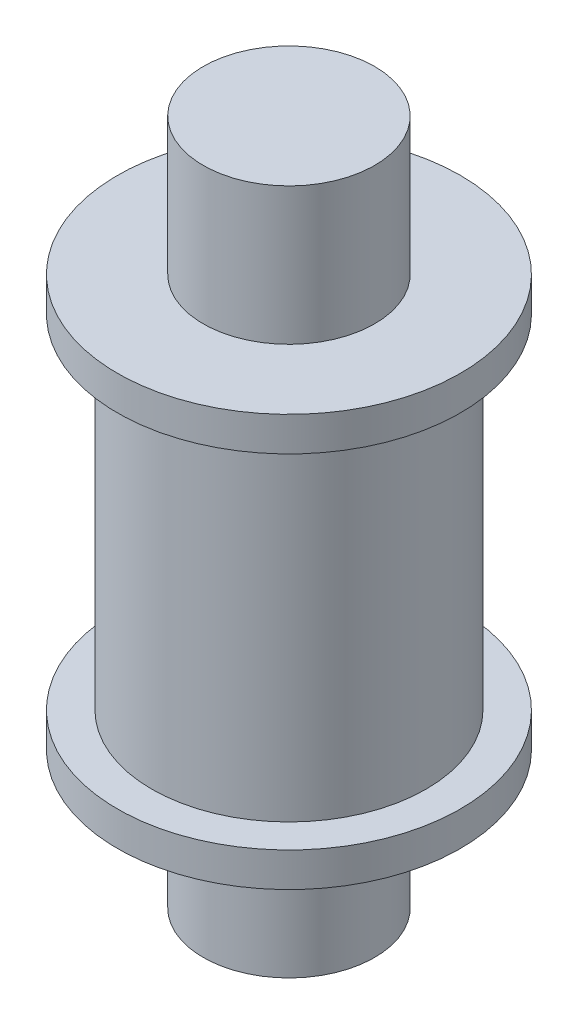
SolidWorks part; units mm, degrees
other "Camera1"
material "Commercial Bronze, UNS C22000 (90-10 Bronze)"
ref_plane "Plan de face" through (0, 0, 0) normal (0, 0, 1) x (1, 0, 0)
ref_plane "Plan de dessus" through (0, 0, 0) normal (0, 1, 0) x (1, 0, 0)
ref_plane "Plan de droite" through (0, 0, 0) normal (1, 0, 0) x (0, 0, -1)
sketch "Sketch1" plane through (0, 0, 0) normal (0, 0, 1) x (1, 0, 0)
  line L0 (10, -20) -> (0, -20)
  line L1 (10, -20) -> (10, 20)
  line L2 (0, -20) -> (0, 20)
  line L3 (10, 20) -> (0, 20)
  line L4 (10, -20) -> (0, 20) construction
  line L5 (0, -20) -> (10, 20) construction
  line L6 (5, 20) -> (5, 12)
  line L7 (5, 12) -> (10, 12)
  line L8 (10, 10) -> (8, 10)
  line L9 (8, 10) -> (8, -10)
  line L10 (0, 0) -> (10, 0) construction
  line L11 (10, -10) -> (8, -10)
  line L12 (5, -12) -> (10, -12)
  line L13 (5, -20) -> (5, -12)
  point P1 (5, 0)
  point P14 (0, 0)
  point P16 (8, 0)
  point P20 (11.1396, 20)
  point P21 (12.3216, -10)
  dimension "D1" = 5
  dimension "D2" = 40
  dimension "D3" = 8
  dimension "D4" = 20
  dimension "D5" = 10
  dimension "D6" = 8
revolve "Revolve1" add sketch "Sketch1" angle 360 about L2 region at (3.7143, 0, 0)
